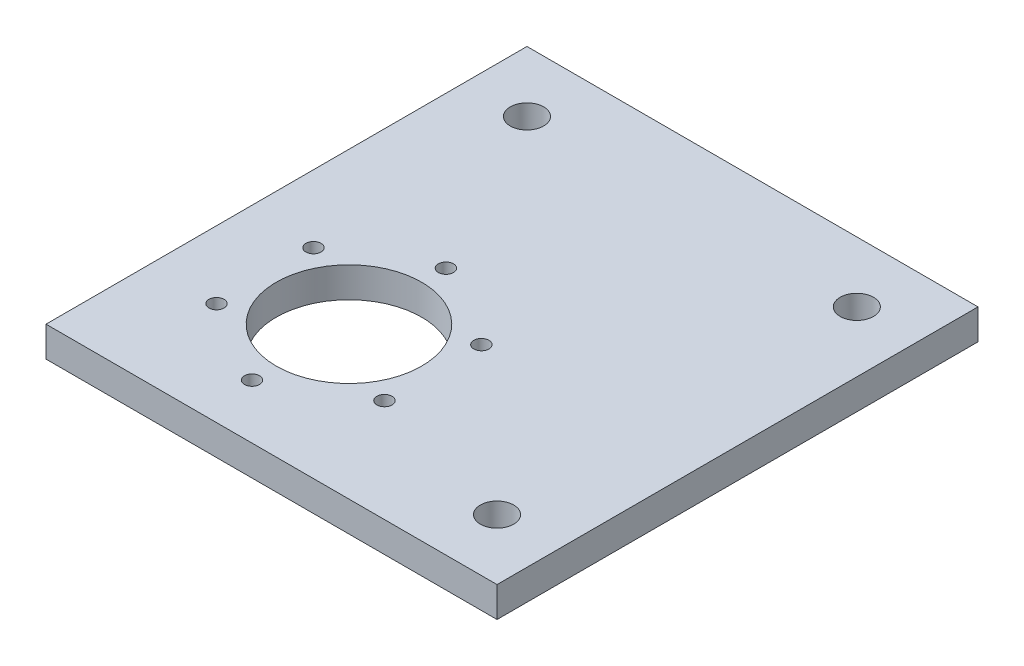
SolidWorks part; units mm, degrees
ref_plane "Front Plane" through (0, 0, 0) normal (0, 0, 1) x (1, 0, 0)
ref_plane "Top Plane" through (0, 0, 0) normal (0, 1, 0) x (1, 0, 0)
ref_plane "Right Plane" through (0, 0, 0) normal (1, 0, 0) x (0, 0, -1)
sketch "Sketch2" plane through (0, 0, 0) normal (0, 1, 0) x (1, 0, 0)
  line L1 (-18.6933, 53.5256) -> (55.7467, 53.5256)
  line L2 (-18.6933, 53.5256) -> (-18.6933, -25.8544)
  line L3 (-18.6933, -25.8544) -> (55.7467, -25.8544)
  line L4 (55.7467, 53.5256) -> (55.7467, -25.8544)
  circle A0 centre (6.3067, -0.8544) radius 12
  dimension "D1" = 24
  dimension "D2" = 74.44
  dimension "D3" = 79.38
extrude "Boss-Extrude1" add sketch "Sketch2" along normal blind 5
sketch "Sketch4" plane through (0, 5, 0) normal (0, 1, 0) x (1, 0, 0)
  circle A0 centre (6.3067, 15.1456) radius 1.25 construction
  circle A1 centre (6.3067, 15.1456) radius 1.25
  circle A2 centre (6.3067, -16.8544) radius 1.25 construction
  circle A3 centre (6.3067, -16.8544) radius 1.25
  circle A4 centre (-7.5497, -8.8544) radius 1.25 construction
  circle A5 centre (-7.5497, -8.8544) radius 1.25
  circle A6 centre (-7.5497, -8.8544) radius 1.25 construction
  circle A7 centre (-7.5497, -8.8544) radius 1.25
  circle A8 centre (-7.5497, 7.1456) radius 1.25 construction
  circle A9 centre (-7.5497, 7.1456) radius 1.25
  circle A10 centre (20.1631, 7.1456) radius 1.25 construction
  circle A11 centre (20.1631, 7.1456) radius 1.25
  circle A12 centre (20.1631, -8.8544) radius 1.25 construction
  circle A13 centre (20.1631, -8.8544) radius 1.25
sketch "Sketch5" plane through (0, 5, 0) normal (0, 1, 0) x (1, 0, 0)
  circle A0 centre (6.3067, 15.1456) radius 1.25
  circle A1 centre (20.1631, 7.1456) radius 1.25
  circle A2 centre (20.1631, -8.8544) radius 1.25
  circle A4 centre (6.3067, -16.8544) radius 1.25
  circle A5 centre (-7.5497, -8.8544) radius 1.25
  circle A6 centre (-7.5497, 7.1456) radius 1.25
  dimension "D1" = 2.5
  dimension "D2" = 2.5
  dimension "D3" = 2.5
  dimension "D4" = 2.5
  dimension "D5" = 2.5
  dimension "D6" = 2.5
extrude "Cut-Extrude1" cut sketch "Sketch5" against normal blind 6
sketch "Sketch6" plane through (0, 0, 0) normal (0, -1, 0) x (1, 0, 0)
  line L0 (55.7467, 25.8544) -> (55.7467, -53.5256) construction
  line L1 (55.7467, -53.5256) -> (-18.6933, -53.5256) construction
  line L2 (-18.6933, 25.8544) -> (55.7467, 25.8544) construction
  line L3 (-18.6933, -53.5256) -> (-18.6933, 25.8544) construction
  circle A0 centre (45.7467, 15.8544) radius 2.75
  circle A2 centre (45.7467, -43.5256) radius 2.75
  circle A3 centre (-8.6933, -43.5256) radius 2.75
  point P10 (0, 0)
  point P13 (0, 0)
  point P14 (0, 0)
  dimension "D5" = 5.5
  dimension "D6" = 5.5
  dimension "D7" = 5.5
  dimension "D1" = 10
  dimension "D2" = 10
  dimension "D3" = 10
  dimension "D4" = 10
extrude "Cut-Extrude2" cut sketch "Sketch6" against normal blind 10
